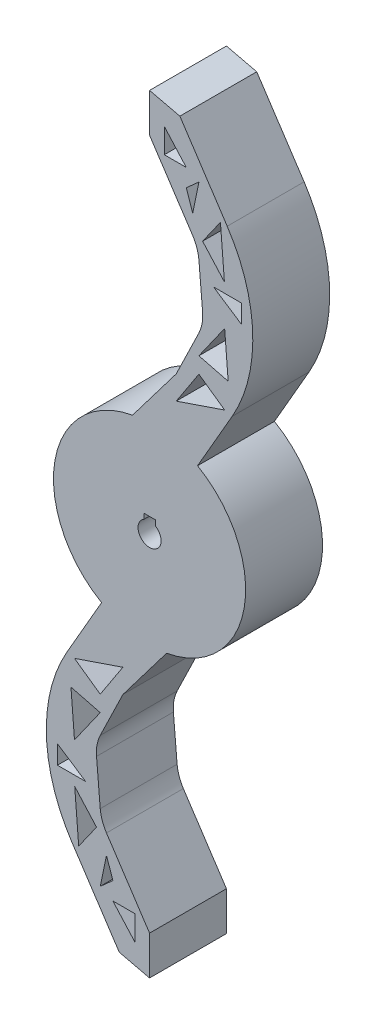
SolidWorks part; units mm, degrees
ref_plane "Front Plane" through (0, 0, 0) normal (0, 0, 1) x (1, 0, 0)
ref_plane "Top Plane" through (0, 0, 0) normal (0, 1, 0) x (1, 0, 0)
ref_plane "Right Plane" through (0, 0, 0) normal (1, 0, 0) x (0, 0, -1)
sketch "Sketch1" plane through (0, 0, 0) normal (0, 0, 1) x (1, 0, 0)
  line L0 (0, 100) -> (7.8845, 98.1388)
  line L1 (21.498, 37.3091) -> (12.4815, 21.6613)
  line L2 (0, 100) -> (0, 89.8889)
  line L3 (0, 89.8889) -> (11.214, 72.9211)
  line L4 (6.9409, 39.5949) -> (-4.4269, 24.6049)
  line L5 (7.8845, 98.1388) -> (20.2056, 79.4957)
  line L6 (12.8349, 68.2595) -> (13.8008, 56.9644)
  line L7 (12.8349, 51.7488) -> (6.9409, 39.5949)
  line L8 (0, 0) -> (179.1851, 0) construction
  line L9 (3.8372, 93.8023) -> (3.8372, 87.4151)
  line L10 (3.8372, 87.4151) -> (9.5461, 87.4151)
  line L11 (9.5461, 87.4151) -> (3.8372, 93.8023)
  line L12 (12.8349, 85.7668) -> (9.5461, 82.8272)
  line L13 (9.5461, 82.8272) -> (11.214, 77.9372)
  line L14 (11.214, 77.9372) -> (12.8349, 85.7668)
  line L15 (18.44, 79.4957) -> (13.8008, 72.9211)
  line L16 (13.8008, 72.9211) -> (19.4742, 66.5736)
  line L17 (19.4742, 66.5736) -> (18.44, 79.4957)
  line L18 (16.6375, 64.0382) -> (23.9688, 64.0382)
  line L19 (23.9688, 64.0382) -> (23.9688, 59.1876)
  line L20 (23.9688, 59.1876) -> (16.6375, 64.0382)
  line L21 (12.8349, 46.6192) -> (19.5334, 56.1123)
  line L22 (19.5334, 56.1123) -> (20.4483, 44.681)
  line L23 (20.4483, 44.681) -> (12.8349, 46.6192)
  line L24 (6.9409, 33.4506) -> (19.5334, 37.7457)
  line L25 (19.5334, 37.7457) -> (12.8349, 42.4722)
  line L26 (12.8349, 42.4722) -> (6.9409, 33.4506)
  line L27 (0, 0) -> (0, -108.1972) construction
  line L54 (0, -100) -> (-7.8845, -98.1388)
  line L55 (-21.498, -37.3091) -> (-12.4815, -21.6613)
  line L56 (0, -100) -> (0, -89.8889)
  line L57 (0, -89.8889) -> (-11.214, -72.9211)
  line L58 (-6.9409, -39.5949) -> (4.4269, -24.6049)
  line L59 (-7.8845, -98.1388) -> (-20.2056, -79.4957)
  line L60 (-12.8349, -68.2595) -> (-13.8008, -56.9644)
  line L61 (-12.8349, -51.7488) -> (-6.9409, -39.5949)
  line L62 (-3.8372, -93.8023) -> (-3.8372, -87.4151)
  line L63 (-3.8372, -87.4151) -> (-9.5461, -87.4151)
  line L64 (-9.5461, -87.4151) -> (-3.8372, -93.8023)
  line L65 (-12.8349, -85.7668) -> (-9.5461, -82.8272)
  line L66 (-9.5461, -82.8272) -> (-11.214, -77.9372)
  line L67 (-11.214, -77.9372) -> (-12.8349, -85.7668)
  line L68 (-18.44, -79.4957) -> (-13.8008, -72.9211)
  line L69 (-13.8008, -72.9211) -> (-19.4742, -66.5736)
  line L70 (-19.4742, -66.5736) -> (-18.44, -79.4957)
  line L71 (-16.6375, -64.0382) -> (-23.9688, -64.0382)
  line L72 (-23.9688, -64.0382) -> (-23.9688, -59.1876)
  line L73 (-23.9688, -59.1876) -> (-16.6375, -64.0382)
  line L74 (-12.8349, -46.6192) -> (-19.5334, -56.1123)
  line L75 (-19.5334, -56.1123) -> (-20.4483, -44.681)
  line L76 (-20.4483, -44.681) -> (-12.8349, -46.6192)
  line L77 (-6.9409, -33.4506) -> (-19.5334, -37.7457)
  line L78 (-19.5334, -37.7457) -> (-12.8349, -42.4722)
  line L79 (-12.8349, -42.4722) -> (-6.9409, -33.4506)
  circle A0 centre (0, 0) radius 100 construction
  circle A1 centre (0, 0) radius 25
  arc A2 (13.8008, 56.9644) -> (12.8349, 51.7488) centre (3.8372, 56.1123) cw
  arc A3 (20.2056, 79.4957) -> (21.498, 37.3091) centre (-13.2934, 57.3564) cw
  arc A4 (11.214, 72.9211) -> (12.8349, 68.2595) centre (2.8713, 67.4075) cw
  arc A8 (-13.8008, -56.9644) -> (-12.8349, -51.7488) centre (-3.8372, -56.1123) cw
  arc A9 (-20.2056, -79.4957) -> (-21.498, -37.3091) centre (13.2934, -57.3564) cw
  arc A10 (-11.214, -72.9211) -> (-12.8349, -68.2595) centre (-2.8713, -67.4075) cw
  dimension "D1" = 200
  dimension "D2" = 10
  dimension "30" = 50
extrude "Boss-Extrude2" add sketch "Sketch1" along normal mid plane 20 contours A1 | A1 region at (0, 0, 0)
extrude "Boss-Extrude3" add sketch "Sketch1<3>" along normal mid plane 20 contours L3 A4 L6 A2 L7 L4 A1 L1 A3 L5 L0 L2 L22 L23 L21 L19 L20 L18 L11 L10 L9 L14 L13 L12 L17 L16 L15 L26 L25 L24 | L57 A10 L60 A8 L61 L58 A1 L55 A9 L59 L54 L56 L75 L76 L74 L72 L73 L71 L64 L63 L62 L67 L66 L65 L70 L69 L68 L79 L78 L77 region at (3.7484, 98.2484, 0) region at (-1.9291, -31.5902, 0)
sketch "Sketch1<3>" plane through (0, 0, 0) normal (0, 0, 1) x (1, 0, 0) same geometry as "Sketch1"
sketch "Sketch4" plane through (0, 0, -10) normal (0, 0, -1) x (-1, 0, 0)
  circle A0 centre (0, 0) radius 3
  dimension "D1" = 6
extrude "Cut-Extrude2" cut sketch "Sketch4" against normal mid plane 195
sketch "Sketch5" plane through (0, 0, -10) normal (0, 0, -1) x (-1, 0, 0)
  line L1 (-1.5, -1.4379) -> (1.5, -1.4379)
  line L2 (-1.5, -1.4379) -> (-1.5, 3.9982)
  line L3 (-1.5, 3.9982) -> (1.5, 3.9982)
  line L4 (1.5, -1.4379) -> (1.5, 3.9982)
  line L5 (-1.5, -1.4379) -> (1.5, 3.9982) construction
  line L6 (-1.5, 3.9982) -> (1.5, -1.4379) construction
  point P0 (0, 1.2802)
  dimension "D1" = 3
extrude "Cut-Extrude3" cut sketch "Sketch5" against normal mid plane 195
